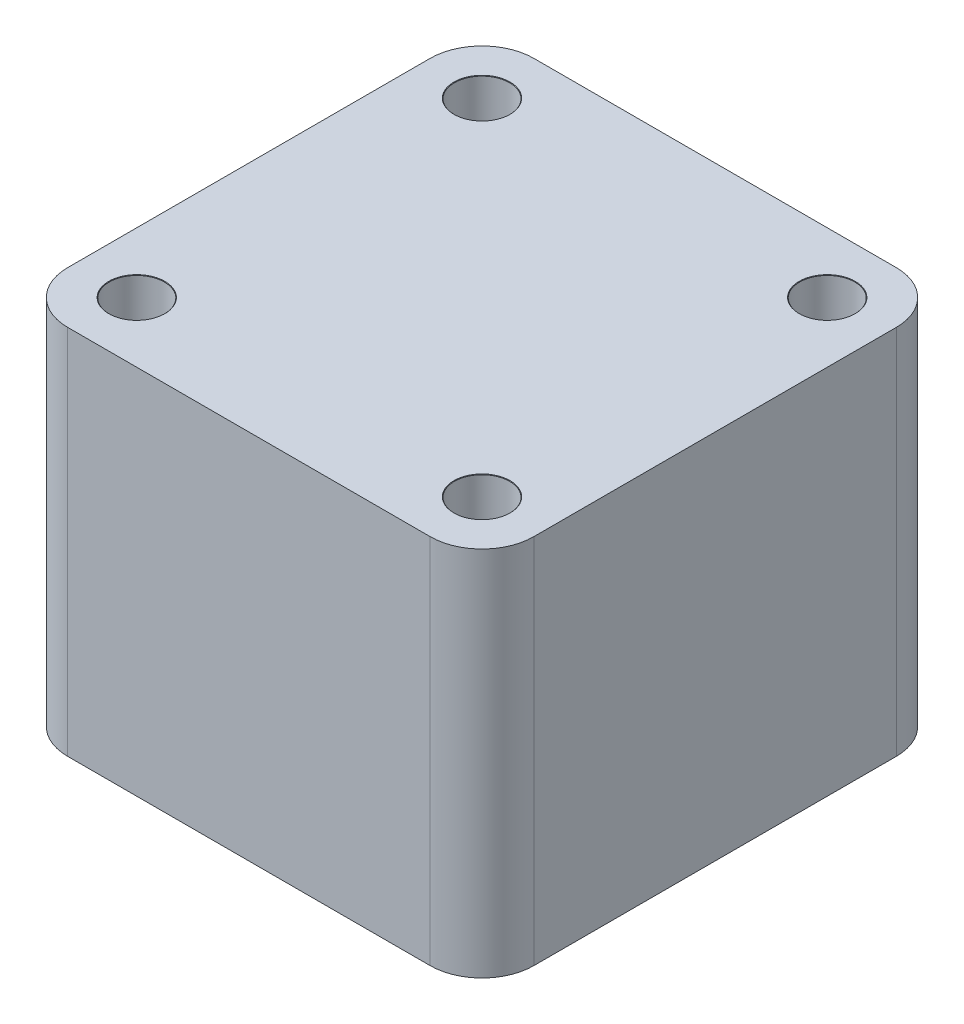
SolidWorks part; units mm, degrees
material "AISI 1045 Steel, cold drawn"
ref_plane "Front Plane" through (0, 0, 0) normal (0, 0, 1) x (1, 0, 0)
ref_plane "Top Plane" through (0, 0, 0) normal (0, 1, 0) x (1, 0, 0)
ref_plane "Right Plane" through (0, 0, 0) normal (1, 0, 0) x (0, 0, -1)
sketch "Sketch1" plane through (0, 0, 0) normal (0, 1, 0) x (1, 0, 0)
  line L1 (13.5, -13.5) -> (-13.5, -13.5)
  line L2 (13.5, -13.5) -> (13.5, 13.5)
  line L3 (13.5, 13.5) -> (-13.5, 13.5)
  line L4 (-13.5, -13.5) -> (-13.5, 13.5)
  line L5 (13.5, -13.5) -> (-13.5, 13.5) construction
  line L6 (13.5, 13.5) -> (-13.5, -13.5) construction
  line L7 (10, -10) -> (-10, -10) construction
  line L8 (10, -10) -> (10, 10) construction
  line L9 (10, 10) -> (-10, 10) construction
  line L10 (-10, -10) -> (-10, 10) construction
  line L11 (10, -10) -> (-10, 10) construction
  line L12 (10, 10) -> (-10, -10) construction
  point P0 (0, 0)
  point P6 (0, 0)
  dimension "D1" = 20
  dimension "D2" = 27
extrude "Boss-Extrude1" add sketch "Sketch1" along normal blind 21.525
hole_wizard "M3 Clearance Hole1" positions "Sketch2" profile "Sketch4" hole size "M3" standard "ANSI Metric" end condition through all
sketch "Sketch2" plane through (0, 0, 0) normal (0, -1, 0) x (-1, 0, 0)
  point P0 (-10, 10)
  point P3 (10, 10)
  point P6 (10, -10)
  point P9 (-10, -10)
sketch "Sketch4" plane through (10, 0, -10) normal (1, 0, 0) x (0, 0, -1)
  line L0 (0, 0) -> (0, 21.525)
  line L1 (0, 21.525) -> (1.625, 21.525)
  line L2 (1.6, 21.5) -> (1.6, 0.025)
  line L3 (1.6, 0.025) -> (1.625, 0)
  line L5 (1.625, 0) -> (0, 0)
  line L6 (-1.6, 0.025) -> (-1.625, 0) construction
  line L7 (1.625, 21.525) -> (1.6, 21.5)
  line L8 (-1.625, 21.525) -> (-1.6, 21.5) construction
  line L11 (0, -6.35) -> (0, 107.95) construction
  dimension "Thru Hole Dia." = 3.2
  dimension "Thru Hole Depth" = 21.525
  dimension "Near C'Sink Dia." = 3.25
  dimension "Near C'Sink Angle" = 90
  dimension "Far C'Sink Dia." = 3.25
  dimension "Far C'Sink Angle" = 90
fillet "Fillet1" radius 3 4 edges at (13.5, 10.7625, 13.5) (-13.5, 10.7625, 13.5) (13.5, 10.7625, -13.5) (-13.5, 10.7625, -13.5)
